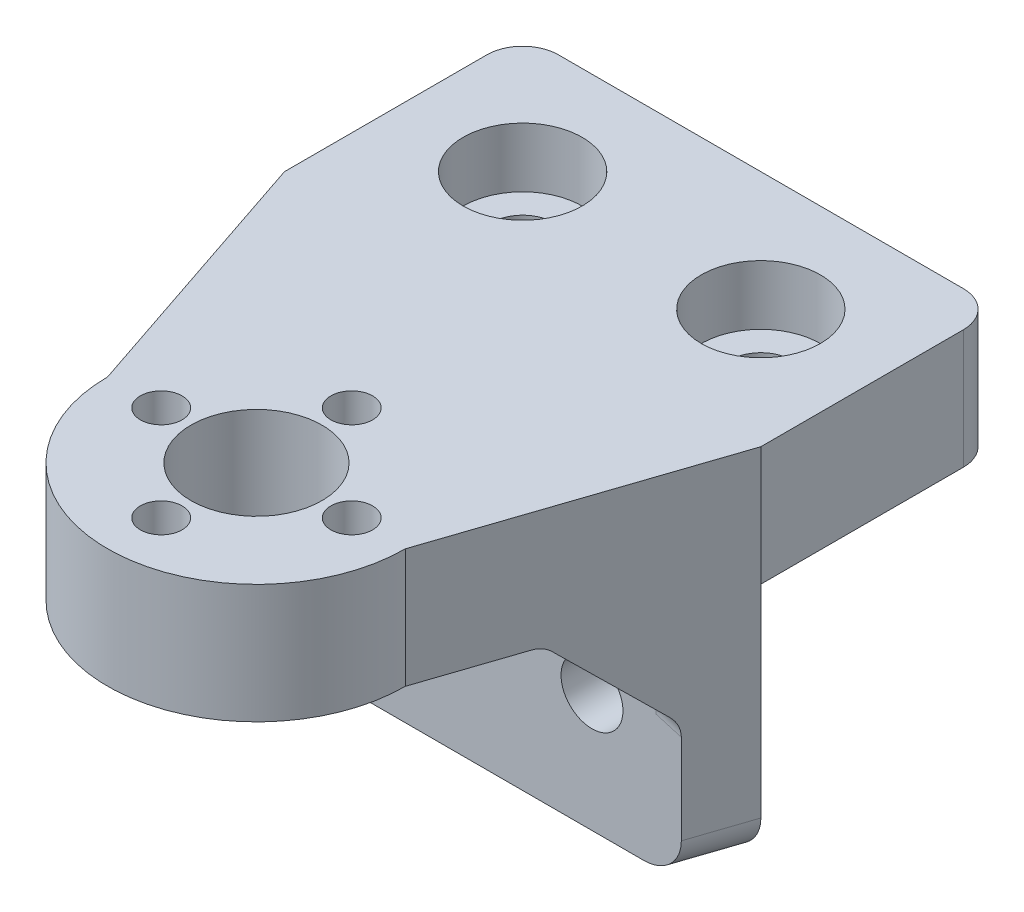
SolidWorks part; units mm, degrees
material "PET"
ref_plane "Front Plane" through (0, 0, 0) normal (0, 0, 1) x (1, 0, 0)
ref_plane "Top Plane" through (0, 0, 0) normal (0, 1, 0) x (1, 0, 0)
ref_plane "Right Plane" through (0, 0, 0) normal (1, 0, 0) x (0, 0, -1)
sketch "Sketch1" plane through (0, 0, 0) normal (0, 1, 0) x (1, 0, 0)
  circle A0 centre (0, 0) radius 12.5
  circle A1 centre (0, 0) radius 5.5
  circle A2 centre (0, 0) radius 8 construction
  circle A3 centre (0, 8) radius 1.75
  circle A4 centre (8, 0) radius 1.75
  circle A5 centre (0, -8) radius 1.75
  circle A6 centre (-8, 0) radius 1.75
  point P16 (0, 0)
  dimension "D1" = 25
  dimension "D2" = 11
  dimension "D3" = 16
  dimension "D4" = 3.5
  dimension "D5" = 4
extrude "Boss-Extrude1" add sketch "Sketch1" along normal blind 10
sketch "Sketch3" plane through (0, 0, 0) normal (0, 1, 0) x (1, 0, 0)
  line L0 (-20, 32.35) -> (20, 32.35) construction
  line L1 (-20, 22.35) -> (20, 22.35) construction
  line L2 (-12.5, 0) -> (-20, 22.35)
  line L3 (-20, 22.35) -> (20, 22.35) construction
  line L4 (12.5, 0) -> (20, 22.35)
  line L5 (-20, 22.35) -> (-20, 42.35)
  line L6 (-20, 42.35) -> (20, 42.35)
  line L7 (20, 22.35) -> (20, 42.35)
  line L8 (0, 0) -> (0, 57.3355) construction
  line L9 (-18.3221, 17.35) -> (18.3221, 17.35) construction
  arc A0 (12.5, 0) -> (-12.5, 0) centre (0, 0) ccw
  circle A1 centre (-10, 32.35) radius 2.6
  circle A2 centre (10, 32.35) radius 2.6
  point P11 (0, 42.35)
  point P16 (0, 0)
  dimension "D1" = 25
  dimension "D2" = 22.35
  dimension "D3" = 20
  dimension "D4" = 5.2
  dimension "D6" = 40
  dimension "D5" = 5.2
  dimension "D7" = 10
  dimension "D8" = 10
  dimension "D9" = 5
extrude "Boss-Extrude2" add sketch "Sketch3" along normal blind 10
sketch "Sketch4" plane through (0, 0, 0) normal (0, 1, 0) x (1, 0, 0)
  line L0 (-20, 32.35) -> (20, 32.35) construction
  line L1 (-20, 22.35) -> (20, 22.35)
  line L2 (-12.5, 0) -> (-20, 22.35)
  line L3 (-20, 22.35) -> (20, 22.35) construction
  line L4 (12.5, 0) -> (20, 22.35)
  line L5 (-20, 22.35) -> (-20, 42.35)
  line L6 (-20, 42.35) -> (20, 42.35)
  line L7 (20, 22.35) -> (20, 42.35)
  line L8 (0, 0) -> (0, 57.3355) construction
  line L9 (-18.3221, 17.35) -> (18.3221, 17.35)
  arc A0 (12.5, 0) -> (-12.5, 0) centre (0, 0) ccw
  circle A1 centre (-10, 32.35) radius 2.6
  circle A2 centre (10, 32.35) radius 2.6
  point P11 (0, 42.35)
  point P16 (0, 0)
  dimension "D1" = 25
  dimension "D2" = 22.35
  dimension "D3" = 20
  dimension "D4" = 5.2
  dimension "D6" = 40
  dimension "D5" = 5.2
  dimension "D7" = 10
  dimension "D8" = 10
  dimension "D9" = 5
extrude "Boss-Extrude3" add sketch "Sketch4" against normal blind 20 contours L2 L9 L4 L1 region at (0, 0, -19.8865)
sketch "Sketch5" plane through (0, 0, -17.35) normal (0, 0, 1) x (1, 0, 0)
  line L0 (-18.3221, -10) -> (18.3221, -10) construction
  line L1 (-18.3221, -20) -> (-18.3221, 0) construction
  line L2 (18.3221, -20) -> (18.3221, 0) construction
  circle A0 centre (-10.8221, -10) radius 2.6
  circle A1 centre (10.8221, -10) radius 2.6
  dimension "D1" = 5.2
  dimension "D2" = 5.2
  dimension "D3" = 7.5
  dimension "D4" = 7.5
extrude "Cut-Extrude1" cut sketch "Sketch5" against normal through all
fillet "Fillet3" radius 3 2 edges at (19.1611, -20, -19.85) (-19.1611, -20, -19.85)
fillet "Fillet4" radius 3 2 edges at (20, 5, -42.35) (-20, 5, -42.35)
sketch "Sketch6" plane through (-11.2349, 0, 3.7701) normal (-0.948, 0, 0.3181) x (0.3181, 0, 0.948)
  line L0 (-22.2775, -8.5) -> (-13.1271, 0)
  line L1 (-22.2775, -17) -> (-22.2775, 0) construction
  line L2 (-22.2775, 0) -> (-3.9767, 0) construction
rib "Rib1" sketch "Sketch6" sketch "Sketch6" thickness 2 extrusion direction parallel to sketch draft on no parameters "D1"=2
fillet "Fillet6" radius 2 2 edges at (-17.2673, -8.1883, -17.35) (-14.463, 0, -8.9931)
sketch "Sketch7" plane through (11.2349, 0, 3.7701) normal (0.948, 0, 0.3181) x (0.3181, 0, -0.948)
  line L0 (22.2775, -8.5) -> (13.1271, 0)
  line L1 (22.2775, -17) -> (22.2775, 0) construction
  line L2 (3.9767, 0) -> (22.2775, 0) construction
rib "Rib2" sketch "Sketch7" sketch "Sketch7" thickness 2 extrusion direction parallel to sketch draft on no parameters "D1"=2
fillet "Fillet7" radius 2 2 edges at (17.2673, -8.1883, -17.35) (14.463, 0, -8.9931)
sketch "Sketch8" plane through (0, 10, 0) normal (0, 1, 0) x (1, 0, 0)
  circle A0 centre (-10, 32.35) radius 5
  circle A1 centre (10, 32.35) radius 5
  dimension "D1" = 10
  dimension "D2" = 10
extrude "Cut-Extrude2" cut sketch "Sketch8" against normal blind 5
